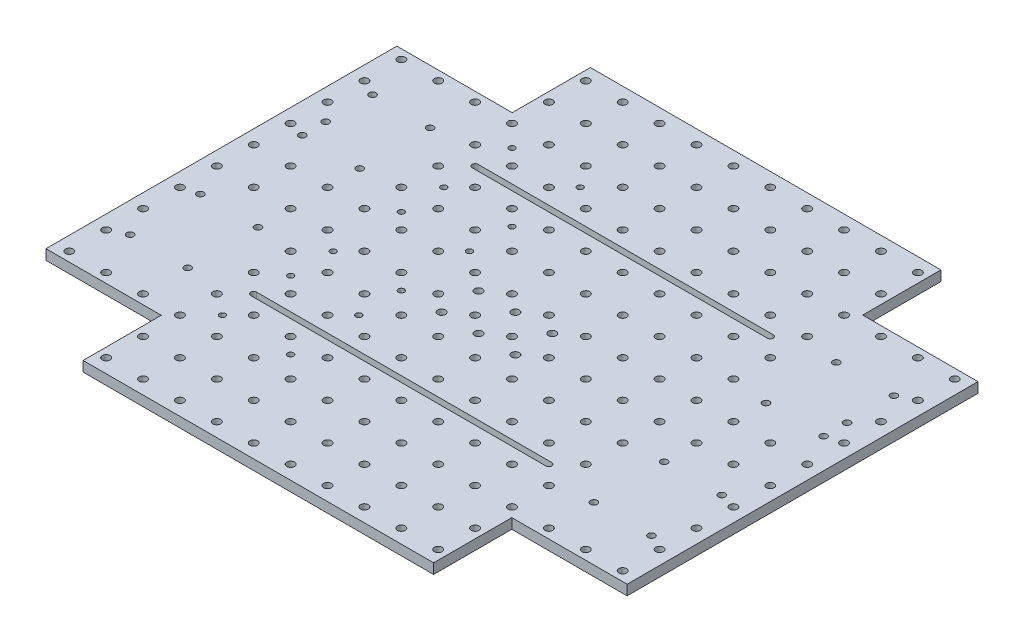
SolidWorks part; units mm, degrees
ref_plane "Front Plane" through (0, 0, 0) normal (0, 0, 1) x (1, 0, 0)
ref_plane "Top Plane" through (0, 0, 0) normal (0, 1, 0) x (1, 0, 0)
ref_plane "Right Plane" through (0, 0, 0) normal (1, 0, 0) x (0, 0, -1)
sketch "Sketch1" plane through (0, 0, 0) normal (0, 1, 0) x (1, 0, 0)
  line L0 (95, -95.1) -> (157.5, -95.1)
  line L1 (-157.5, 95.1) -> (-95, 95.1)
  line L2 (-157.5, 95.1) -> (-157.5, -95.1)
  line L3 (-157.5, -95.1) -> (-95, -95.1)
  line L4 (157.5, 95.1) -> (157.5, -95.1)
  line L5 (-157.5, 95.1) -> (157.5, -95.1) construction
  line L6 (-157.5, -95.1) -> (157.5, 95.1) construction
  line L7 (95, 137.5) -> (-95, 137.5)
  line L8 (95, 137.5) -> (95, 95.1)
  line L9 (95, -137.5) -> (-95, -137.5)
  line L10 (-95, 137.5) -> (-95, 95.1)
  line L11 (95, 137.5) -> (-95, -137.5) construction
  line L12 (95, -137.5) -> (-95, 137.5) construction
  line L13 (95, -95.1) -> (95, -137.5)
  line L14 (-95, -95.1) -> (-95, -137.5)
  line L15 (95, 95.1) -> (157.5, 95.1)
  point P0 (0, 0)
  point P6 (0, 0)
  dimension "D1" = 315
  dimension "D2" = 42.4
  dimension "D3" = 275
  dimension "D4" = 190
extrude "Boss-Extrude1" add sketch "Sketch1" along normal blind 5.4864
sketch "Sketch2" plane through (0, 5.4864, 0) normal (0, 1, 0) x (1, 0, 0)
  line L0 (0, 0) -> (150, 0) construction
  line L1 (150, 0) -> (150, -130) construction
  line L2 (150, -130) -> (130, -130) construction
  line L3 (150, -110) -> (130, -110) construction
  line L4 (150, -90) -> (130, -90) construction
  line L5 (150, -70) -> (130, -70) construction
  line L6 (150, -50) -> (130, -50) construction
  line L7 (150, -30) -> (130, -30) construction
  line L8 (150, -10) -> (130, -10) construction
  line L9 (150, 10) -> (130, 10) construction
  line L10 (150, 30) -> (130, 30) construction
  line L11 (150, 50) -> (130, 50) construction
  line L12 (150, 70) -> (130, 70) construction
  line L13 (150, 90) -> (130, 90) construction
  line L14 (150, 110) -> (130, 110) construction
  line L15 (150, -130) -> (150, -110) construction
  line L16 (150, 130) -> (130, 130) construction
  line L17 (150, 150) -> (130, 150) construction
  circle A0 centre (150, -130) radius 2.1 construction
  circle A1 centre (130, -130) radius 2.1 construction
  circle A2 centre (110, -130) radius 2.1 construction
  circle A3 centre (90, -130) radius 2.1
  circle A4 centre (70, -130) radius 2.1
  circle A5 centre (50, -130) radius 2.1
  circle A6 centre (30, -130) radius 2.1
  circle A7 centre (10, -130) radius 2.1
  circle A8 centre (-10, -130) radius 2.1
  circle A9 centre (-30, -130) radius 2.1
  circle A10 centre (-50, -130) radius 2.1
  circle A11 centre (-70, -130) radius 2.1
  circle A12 centre (-90, -130) radius 2.1
  circle A13 centre (-110, -130) radius 2.1
  circle A14 centre (-130, -130) radius 2.1 construction
  circle A15 centre (-150, -130) radius 2.1 construction
  circle A17 centre (150, -110) radius 2.1 construction
  circle A18 centre (130, -110) radius 2.1 construction
  circle A19 centre (110, -110) radius 2.1 construction
  circle A20 centre (90, -110) radius 2.1
  circle A21 centre (70, -110) radius 2.1
  circle A22 centre (50, -110) radius 2.1
  circle A23 centre (30, -110) radius 2.1
  circle A24 centre (10, -110) radius 2.1
  circle A25 centre (-10, -110) radius 2.1
  circle A26 centre (-30, -110) radius 2.1
  circle A27 centre (-50, -110) radius 2.1
  circle A28 centre (-70, -110) radius 2.1
  circle A29 centre (-90, -110) radius 2.1
  circle A30 centre (-110, -110) radius 2.1
  circle A31 centre (-130, -110) radius 2.1 construction
  circle A32 centre (-150, -110) radius 2.1 construction
  circle A34 centre (150, -90) radius 2.1
  circle A35 centre (130, -90) radius 2.1
  circle A36 centre (110, -90) radius 2.1
  circle A37 centre (90, -90) radius 2.1
  circle A38 centre (70, -90) radius 2.1
  circle A39 centre (50, -90) radius 2.1
  circle A40 centre (30, -90) radius 2.1
  circle A41 centre (10, -90) radius 2.1
  circle A42 centre (-10, -90) radius 2.1
  circle A43 centre (-30, -90) radius 2.1
  circle A44 centre (-50, -90) radius 2.1
  circle A45 centre (-70, -90) radius 2.1
  circle A46 centre (-90, -90) radius 2.1
  circle A47 centre (-110, -90) radius 2.1
  circle A48 centre (-130, -90) radius 2.1
  circle A49 centre (-150, -90) radius 2.1
  circle A51 centre (150, -70) radius 2.1
  circle A52 centre (130, -70) radius 2.1 construction
  circle A53 centre (110, -70) radius 2.1 construction
  circle A54 centre (90, -70) radius 2.1
  circle A55 centre (70, -70) radius 2.1
  circle A56 centre (50, -70) radius 2.1
  circle A57 centre (30, -70) radius 2.1
  circle A58 centre (10, -70) radius 2.1
  circle A59 centre (-10, -70) radius 2.1
  circle A60 centre (-30, -70) radius 2.1
  circle A61 centre (-50, -70) radius 2.1
  circle A62 centre (-70, -70) radius 2.1
  circle A63 centre (-90, -70) radius 2.1
  circle A64 centre (-110, -70) radius 2.1 construction
  circle A65 centre (-130, -70) radius 2.1 construction
  circle A66 centre (-150, -70) radius 2.1
  circle A68 centre (150, -50) radius 2.1
  circle A69 centre (130, -50) radius 2.1 construction
  circle A70 centre (110, -50) radius 2.1 construction
  circle A71 centre (90, -50) radius 2.1
  circle A72 centre (70, -50) radius 2.1
  circle A73 centre (50, -50) radius 2.1
  circle A74 centre (30, -50) radius 2.1
  circle A75 centre (10, -50) radius 2.1
  circle A76 centre (-10, -50) radius 2.1
  circle A77 centre (-30, -50) radius 2.1
  circle A78 centre (-50, -50) radius 2.1
  circle A79 centre (-70, -50) radius 2.1
  circle A80 centre (-90, -50) radius 2.1
  circle A81 centre (-110, -50) radius 2.1 construction
  circle A82 centre (-130, -50) radius 2.1 construction
  circle A83 centre (-150, -50) radius 2.1
  circle A85 centre (150, -30) radius 2.1
  circle A86 centre (130, -30) radius 2.1 construction
  circle A87 centre (110, -30) radius 2.1 construction
  circle A88 centre (90, -30) radius 2.1
  circle A89 centre (70, -30) radius 2.1
  circle A90 centre (50, -30) radius 2.1
  circle A91 centre (30, -30) radius 2.1
  circle A92 centre (10, -30) radius 2.1
  circle A93 centre (-10, -30) radius 2.1
  circle A94 centre (-30, -30) radius 2.1
  circle A95 centre (-50, -30) radius 2.1
  circle A96 centre (-70, -30) radius 2.1
  circle A97 centre (-90, -30) radius 2.1
  circle A98 centre (-110, -30) radius 2.1 construction
  circle A99 centre (-130, -30) radius 2.1 construction
  circle A100 centre (-150, -30) radius 2.1
  circle A102 centre (150, -10) radius 2.1
  circle A103 centre (130, -10) radius 2.1
  circle A104 centre (110, -10) radius 2.1
  circle A105 centre (90, -10) radius 2.1
  circle A106 centre (70, -10) radius 2.1
  circle A107 centre (50, -10) radius 2.1
  circle A108 centre (30, -10) radius 2.1
  circle A109 centre (10, -10) radius 2.1
  circle A110 centre (-10, -10) radius 2.1
  circle A111 centre (-30, -10) radius 2.1
  circle A112 centre (-50, -10) radius 2.1
  circle A113 centre (-70, -10) radius 2.1
  circle A114 centre (-90, -10) radius 2.1
  circle A115 centre (-110, -10) radius 2.1
  circle A116 centre (-130, -10) radius 2.1
  circle A117 centre (-150, -10) radius 2.1
  circle A119 centre (150, 10) radius 2.1
  circle A120 centre (130, 10) radius 2.1
  circle A121 centre (110, 10) radius 2.1
  circle A122 centre (90, 10) radius 2.1
  circle A123 centre (70, 10) radius 2.1
  circle A124 centre (50, 10) radius 2.1
  circle A125 centre (30, 10) radius 2.1
  circle A126 centre (10, 10) radius 2.1
  circle A127 centre (-10, 10) radius 2.1
  circle A128 centre (-30, 10) radius 2.1
  circle A129 centre (-50, 10) radius 2.1
  circle A130 centre (-70, 10) radius 2.1
  circle A131 centre (-90, 10) radius 2.1
  circle A132 centre (-110, 10) radius 2.1
  circle A133 centre (-130, 10) radius 2.1
  circle A134 centre (-150, 10) radius 2.1
  circle A136 centre (150, 30) radius 2.1
  circle A137 centre (130, 30) radius 2.1 construction
  circle A138 centre (110, 30) radius 2.1 construction
  circle A139 centre (90, 30) radius 2.1
  circle A140 centre (70, 30) radius 2.1
  circle A141 centre (50, 30) radius 2.1
  circle A142 centre (30, 30) radius 2.1
  circle A143 centre (10, 30) radius 2.1
  circle A144 centre (-10, 30) radius 2.1
  circle A145 centre (-30, 30) radius 2.1
  circle A146 centre (-50, 30) radius 2.1
  circle A147 centre (-70, 30) radius 2.1
  circle A148 centre (-90, 30) radius 2.1
  circle A149 centre (-110, 30) radius 2.1 construction
  circle A150 centre (-130, 30) radius 2.1 construction
  circle A151 centre (-150, 30) radius 2.1
  circle A153 centre (150, 50) radius 2.1
  circle A154 centre (130, 50) radius 2.1 construction
  circle A155 centre (110, 50) radius 2.1 construction
  circle A156 centre (90, 50) radius 2.1
  circle A157 centre (70, 50) radius 2.1
  circle A158 centre (50, 50) radius 2.1
  circle A159 centre (30, 50) radius 2.1
  circle A160 centre (10, 50) radius 2.1
  circle A161 centre (-10, 50) radius 2.1
  circle A162 centre (-30, 50) radius 2.1
  circle A163 centre (-50, 50) radius 2.1
  circle A164 centre (-70, 50) radius 2.1
  circle A165 centre (-90, 50) radius 2.1
  circle A166 centre (-110, 50) radius 2.1 construction
  circle A167 centre (-130, 50) radius 2.1 construction
  circle A168 centre (-150, 50) radius 2.1
  circle A170 centre (150, 70) radius 2.1
  circle A171 centre (130, 70) radius 2.1 construction
  circle A172 centre (110, 70) radius 2.1 construction
  circle A173 centre (90, 70) radius 2.1
  circle A174 centre (70, 70) radius 2.1
  circle A175 centre (50, 70) radius 2.1
  circle A176 centre (30, 70) radius 2.1
  circle A177 centre (10, 70) radius 2.1
  circle A178 centre (-10, 70) radius 2.1
  circle A179 centre (-30, 70) radius 2.1
  circle A180 centre (-50, 70) radius 2.1
  circle A181 centre (-70, 70) radius 2.1
  circle A182 centre (-90, 70) radius 2.1
  circle A183 centre (-110, 70) radius 2.1 construction
  circle A184 centre (-130, 70) radius 2.1 construction
  circle A185 centre (-150, 70) radius 2.1
  circle A187 centre (150, 90) radius 2.1
  circle A188 centre (130, 90) radius 2.1
  circle A189 centre (110, 90) radius 2.1
  circle A190 centre (90, 90) radius 2.1
  circle A191 centre (70, 90) radius 2.1
  circle A192 centre (50, 90) radius 2.1
  circle A193 centre (30, 90) radius 2.1
  circle A194 centre (10, 90) radius 2.1
  circle A195 centre (-10, 90) radius 2.1
  circle A196 centre (-30, 90) radius 2.1
  circle A197 centre (-50, 90) radius 2.1
  circle A198 centre (-70, 90) radius 2.1
  circle A199 centre (-90, 90) radius 2.1
  circle A200 centre (-110, 90) radius 2.1
  circle A201 centre (-130, 90) radius 2.1
  circle A202 centre (-150, 90) radius 2.1
  circle A204 centre (150, 110) radius 2.1
  circle A205 centre (130, 110) radius 2.1
  circle A206 centre (110, 110) radius 2.1
  circle A207 centre (90, 110) radius 2.1
  circle A208 centre (70, 110) radius 2.1
  circle A209 centre (50, 110) radius 2.1
  circle A210 centre (30, 110) radius 2.1
  circle A211 centre (10, 110) radius 2.1
  circle A212 centre (-10, 110) radius 2.1
  circle A213 centre (-30, 110) radius 2.1
  circle A214 centre (-50, 110) radius 2.1
  circle A215 centre (-70, 110) radius 2.1
  circle A216 centre (-90, 110) radius 2.1
  circle A217 centre (-110, 110) radius 2.1
  circle A218 centre (-130, 110) radius 2.1
  circle A219 centre (-150, 110) radius 2.1
  circle A221 centre (150, 130) radius 2.1 construction
  circle A222 centre (130, 130) radius 2.1 construction
  circle A223 centre (110, 130) radius 2.1
  circle A224 centre (90, 130) radius 2.1
  circle A225 centre (70, 130) radius 2.1
  circle A226 centre (50, 130) radius 2.1
  circle A227 centre (30, 130) radius 2.1
  circle A228 centre (10, 130) radius 2.1
  circle A229 centre (-10, 130) radius 2.1
  circle A230 centre (-30, 130) radius 2.1
  circle A231 centre (-50, 130) radius 2.1
  circle A232 centre (-70, 130) radius 2.1
  circle A233 centre (-90, 130) radius 2.1
  circle A234 centre (-110, 130) radius 2.1
  circle A235 centre (-130, 130) radius 2.1 construction
  circle A236 centre (-150, 130) radius 2.1 construction
  circle A238 centre (150, 150) radius 2.1 construction
  circle A239 centre (130, 150) radius 2.1 construction
  circle A240 centre (110, 150) radius 2.1 construction
  circle A241 centre (90, 150) radius 2.1
  circle A242 centre (70, 150) radius 2.1
  circle A243 centre (50, 150) radius 2.1
  circle A244 centre (30, 150) radius 2.1
  circle A245 centre (10, 150) radius 2.1
  circle A246 centre (-10, 150) radius 2.1
  circle A247 centre (-30, 150) radius 2.1
  circle A248 centre (-50, 150) radius 2.1
  circle A249 centre (-70, 150) radius 2.1
  circle A250 centre (-90, 150) radius 2.1
  circle A251 centre (-110, 150) radius 2.1
  circle A252 centre (-130, 150) radius 2.1 construction
  circle A253 centre (-150, 150) radius 2.1 construction
  dimension "D3" = 4.2
  dimension "D1" = 150
  dimension "D2" = 130
  dimension "D5" = 20
  dimension "D7" = 20
  dimension "D4" = 16
  dimension "D6" = 15
extrude "Cut-Extrude1" cut sketch "Sketch2" against normal through all
hole_wizard "Ø3.0mm Clearance Dowel Hole1" positions "Sketch3" profile "Sketch4" hole size "Ø3.0" standard "ANSI Metric" end condition through all
sketch "Sketch3" plane through (-115.8567, 5.4864, -238.7408) normal (0, 1, 0) x (1, 0, 0)
  point P0 (-25.4433, -173.0408)
  point P3 (5.7567, -173.0408)
  point P6 (-25.4433, -211.1408)
  point P9 (5.7567, -211.1408)
  point P12 (225.9567, -173.0408)
  point P15 (257.1567, -173.0408)
  point P18 (225.9567, -211.1408)
  point P21 (257.1567, -211.1408)
  point P24 (225.9567, -304.4408)
  point P27 (225.9567, -266.3408)
  point P30 (257.1567, -266.3408)
  point P33 (257.1567, -304.4408)
  point P36 (-25.4433, -266.3408)
  point P39 (-25.4433, -304.4408)
  point P42 (5.7567, -304.4408)
  point P45 (5.7567, -266.3408)
  point P48 (-25.4433, -198.4408)
  point P51 (257.1567, -198.4408)
sketch "Sketch4" plane through (-141.3, 5.4864, -65.7) normal (1, 0, 0) x (0, 0, 1)
  line L0 (0, 0) -> (0, 5.4864)
  line L1 (0, 5.4864) -> (1.85, 5.4864)
  line L2 (1.85, 5.4864) -> (1.85, 0)
  line L3 (1.85, 0) -> (0, 0)
  line L4 (0, -6.35) -> (0, 107.95) construction
  dimension "Thru Hole Dia." = 3.7
  dimension "Thru Hole Depth" = 5.4864
sketch "Sketch5" plane through (0, 5.4864, 0) normal (0, 1, 0) x (1, 0, 0)
  line L0 (-30, 130) -> (-10, 130) construction
  line L1 (-10, 130) -> (-20.47, 130) construction
  line L2 (-20.47, 130) -> (-20.47, 2.3) construction
  line L3 (-20.47, 2.3) -> (-0.47, 2.3) construction
  line L4 (-20.47, -17.7) -> (-0.47, -17.7) construction
  line L5 (-20.47, 2.3) -> (-20.47, -17.7) construction
  circle A0 centre (-20.47, 2.3) radius 2.1
  circle A1 centre (-0.47, 2.3) radius 2.1
  circle A2 centre (19.53, 2.3) radius 2.1
  circle A3 centre (-20.47, -17.7) radius 2.1
  circle A4 centre (-0.47, -17.7) radius 2.1
  circle A5 centre (19.53, -17.7) radius 2.1
  dimension "D2" = 4.2
  dimension "D1" = 127.7
  dimension "D4" = 20
  dimension "D6" = 20
  dimension "D7" = 9.53
  dimension "D3" = 3
  dimension "D5" = 2
extrude "Cut-Extrude2" cut sketch "Sketch5" against normal through all
sketch "Sketch6" plane through (0, 5.4864, 0) normal (0, 1, 0) x (1, 0, 0)
  line L0 (-80, 60) -> (80, 60) construction
  line L1 (-80, -60) -> (80, -60) construction
  line L2 (-80, -60) -> (-80, 60) construction
  line L3 (-80, 60) -> (80, 60) construction
  line L4 (80, -60) -> (80, 60) construction
  line L5 (-80, -60) -> (80, 60) construction
  line L6 (-80, 60) -> (80, -60) construction
  line L7 (-80, 61.6) -> (80, 61.6)
  line L8 (-80, 58.4) -> (80, 58.4)
  line L9 (-80, -60) -> (80, -60) construction
  line L10 (-80, -58.4) -> (80, -58.4)
  line L11 (-80, -61.6) -> (80, -61.6)
  arc A0 (-80, 61.6) -> (-80, 58.4) centre (-80, 60) ccw
  arc A1 (80, 58.4) -> (80, 61.6) centre (80, 60) ccw
  arc A2 (-80, -58.4) -> (-80, -61.6) centre (-80, -60) ccw
  arc A3 (80, -61.6) -> (80, -58.4) centre (80, -60) ccw
  point P0 (0, 0)
  point P6 (0, 60)
  point P11 (0, -60)
  dimension "D1" = 120
  dimension "D2" = 160
  dimension "D3" = 3.2
extrude "Cut-Extrude3" cut sketch "Sketch6" against normal through all
sketch "Sketch7" plane through (0, 5.4864, 0) normal (0, 1, 0) x (1, 0, 0)
  line L0 (-78.475, 41.525) -> (-41.525, 41.525) construction
  line L1 (-78.475, -18.475) -> (-41.525, -18.475) construction
  line L2 (-78.475, -18.475) -> (-78.475, 18.475) construction
  line L3 (-78.475, 18.475) -> (-41.525, 18.475) construction
  line L4 (-41.525, -18.475) -> (-41.525, 18.475) construction
  line L5 (-78.475, -18.475) -> (-41.525, 18.475) construction
  line L6 (-78.475, 18.475) -> (-41.525, -18.475) construction
  line L7 (-78.475, 41.525) -> (-78.475, 78.475) construction
  line L8 (-78.475, 78.475) -> (-41.525, 78.475) construction
  line L9 (-41.525, 41.525) -> (-41.525, 78.475) construction
  line L10 (-78.475, 41.525) -> (-41.525, 78.475) construction
  line L11 (-78.475, 78.475) -> (-41.525, 41.525) construction
  line L12 (-78.475, -78.475) -> (-41.525, -78.475) construction
  line L13 (-78.475, -78.475) -> (-78.475, -41.525) construction
  line L14 (-78.475, -41.525) -> (-41.525, -41.525) construction
  line L15 (-41.525, -78.475) -> (-41.525, -41.525) construction
  line L16 (-78.475, -78.475) -> (-41.525, -41.525) construction
  line L17 (-78.475, -41.525) -> (-41.525, -78.475) construction
  line L18 (-60, 60) -> (-60, -60) construction
  line L21 (-157.5, 0) -> (157.5, 0) construction
  line L22 (-157.5, 95.1) -> (-157.5, -95.1) construction
  line L23 (157.5, -95.1) -> (157.5, 95.1) construction
  line L24 (-70, 70) -> (-50, 70) construction
  line L25 (-60, 70) -> (-60, 78.475) construction
  circle A0 centre (-78.475, 18.475) radius 1.6
  circle A1 centre (-78.475, -18.475) radius 1.6
  circle A2 centre (-41.525, -18.475) radius 1.6
  circle A3 centre (-41.525, 18.475) radius 1.6
  circle A4 centre (-78.475, 78.475) radius 1.6
  circle A5 centre (-78.475, 41.525) radius 1.6
  circle A6 centre (-41.525, 41.525) radius 1.6
  circle A7 centre (-41.525, 78.475) radius 1.6
  circle A8 centre (-78.475, -41.525) radius 1.6
  circle A9 centre (-78.475, -78.475) radius 1.6
  circle A10 centre (-41.525, -78.475) radius 1.6
  circle A11 centre (-41.525, -41.525) radius 1.6
  point P0 (-60, 0)
  point P9 (-60, 60)
  point P18 (-60, -60)
  point P35 (-60, 0)
  dimension "D1" = 3.2
  dimension "D2" = 36.95
  dimension "D3" = 36.95
  dimension "D4" = 36.95
  dimension "D5" = 60
extrude "Cut-Extrude4" cut sketch "Sketch7" against normal through all
